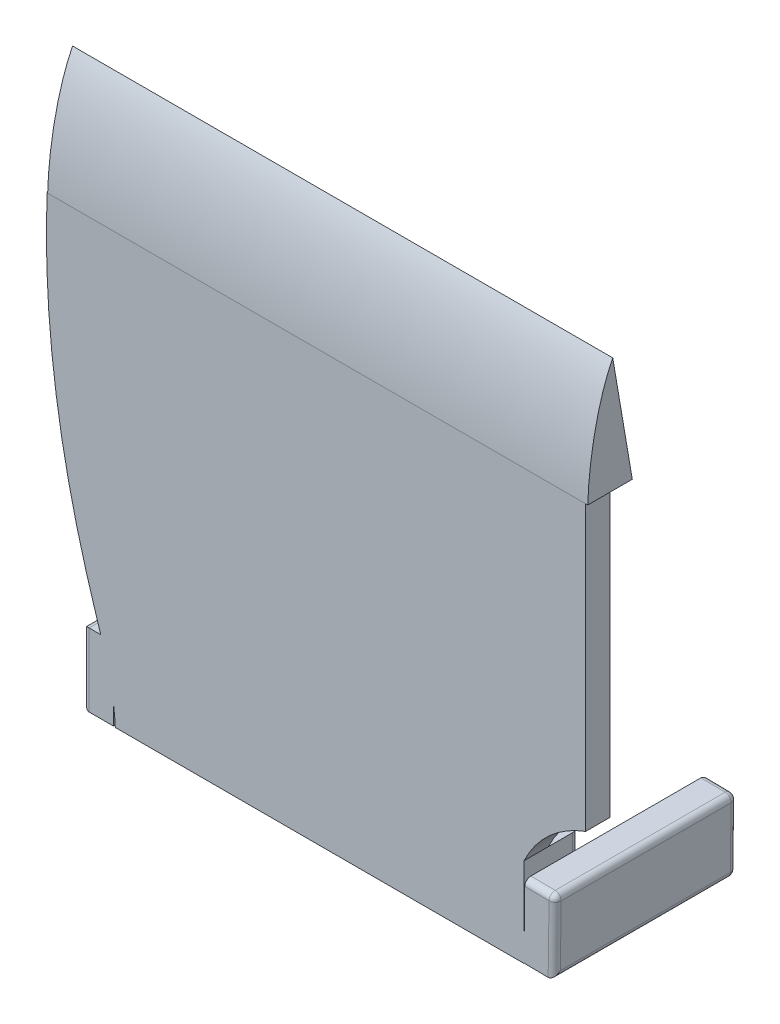
SolidWorks part; units mm, degrees
ref_plane "Front" through (0, 0, 0) normal (0, 0, 1) x (1, 0, 0)
ref_plane "Top" through (0, 0, 0) normal (0, 1, 0) x (1, 0, 0)
ref_plane "Right" through (0, 0, 0) normal (1, 0, 0) x (0, 0, -1)
sketch "Sketch1" plane through (0, 0, 0) normal (0, 0, 1) x (1, 0, 0)
  line L1 (44.1382, -8.5873) -> (44.1382, 38.1814)
  line L2 (44.1382, 38.1814) -> (-44.5905, 38.1814)
  line L3 (17.3145, -37.8937) -> (17.3145, 18.6563) construction
  line L4 (-33.6659, -37.8937) -> (-33.6659, -45.6483)
  line L8 (33.7953, -45.6483) -> (34.0118, -29.1808)
  line L9 (-33.6659, -45.6483) -> (33.7953, -45.6483)
  line L10 (34.0118, -17.8121) -> (34.0118, -29.1808)
  arc A1 (34.0118, -17.8121) -> (44.1382, -8.5873) centre (50.2048, -25.4173) cw
  spline S0 degree 3 poles (-44.5905, 38.1814) (-45.0011, 27.8073) (-43.8008, 9.7168) (-37.8707, -15.3231) (-32.3413, -29.9511) (-33.6659, -37.8937) knots 0 0 0 0 0.403328 0.698479 1 1 1 1
  dimension "D4" = 88.7287
extrude "Boss-Extrude1" add sketch "Sketch1" along normal blind 4
sketch "Sketch2" plane through (0, 0, 0) normal (1, 0, 0) x (0, 0, -1)
  line L3 (3.33, 38.1814) -> (0.1103, 57.1196)
  line L4 (0.1103, 57.1196) -> (-1.7343, 53.5468) construction
  line L5 (-1.7343, 53.5468) -> (-3.1481, 48.2225) construction
  line L6 (-4, 38.1814) -> (3.33, 38.1814)
  line L7 (-3.1481, 48.2225) -> (-3.87, 42.7778) construction
  line L8 (-3.87, 42.7778) -> (-4, 38.1814) construction
  spline S0 degree 4 poles (0.1103, 57.1196) (-1.7343, 53.5468) (-3.1481, 48.2225) (-3.87, 42.7778) (-4, 38.1814) knots 0 0 0 0 0 1 1 1 1 1
  point P2 (-1.5237, 53.8476)
  point P4 (-1.7343, 53.5468)
  point P6 (-3.1481, 48.2225)
  point P8 (-3.87, 42.7778)
  dimension "D1" = 19.21
  dimension "D4" = 7.33
extrude "Boss-Extrude2" add sketch "Sketch2" along normal mid plane 89
ref_plane "Plane1" through (0, 0, 0) normal (0, 0, -1) x (-1, 0, 0)
sketch "Sketch3" plane through (0, 0, 0) normal (0, 0, -1) x (-1, 0, 0)
  line L0 (33.6659, -45.6483) -> (-33.7953, -45.6483) construction
  line L5 (-29.0118, -17.8121) -> (-34.0118, -17.8121)
  line L6 (-29.0118, -17.8121) -> (-29.0118, -45.6483)
  line L15 (-29.0118, -45.6483) -> (-34.0118, -45.6483)
  line L17 (-34.0118, -17.8121) -> (-34.0118, -45.6483)
  line L27 (33.6659, -45.6483) -> (28.6659, -45.6483)
  line L28 (33.6659, -45.6483) -> (33.6659, -17.8121)
  line L29 (33.6659, -17.8121) -> (28.6659, -17.8121)
  line L30 (28.6659, -45.6483) -> (28.6659, -17.8121)
  dimension "D1" = 5
  dimension "D2" = 5
extrude "Boss-Extrude3" add sketch "Sketch3" along normal blind 5
ref_plane "Plane2" through (34.3896, -0.4522, 0) normal (0.9999, -0.0131, 0) x (0, 0, -1)
sketch "Sketch4" plane through (34.3896, -0.4522, 0) normal (0.9999, -0.0131, 0) x (0, 0, -1)
  line L0 (-4, -45.2) -> (-4, -28.7311) construction
  line L1 (-4, -19.9948) -> (26, -19.9948)
  line L2 (-4, -19.9948) -> (-4, -31.9948)
  line L3 (-4, -31.9948) -> (26, -31.9948)
  line L4 (26, -19.9948) -> (26, -31.9948)
  dimension "D1" = 30
  dimension "D2" = 12
extrude "Boss-Extrude4" add sketch "Sketch4" along normal blind 5
ref_plane "Plane3" through (-33.6659, 0, 0) normal (-1, 0, 0) x (0, 0, 1)
sketch "Sketch5" plane through (-33.6659, 0, 0) normal (-1, 0, 0) x (0, 0, 1)
  line L0 (4, -37.8937) -> (4, -45.6483) construction
  line L1 (-26, -20.4453) -> (4, -20.4453)
  line L2 (-26, -20.4453) -> (-26, -32.4453)
  line L3 (-26, -32.4453) -> (4, -32.4453)
  line L4 (4, -20.4453) -> (4, -32.4453)
  dimension "D1" = 12
extrude "Boss-Extrude5" add sketch "Sketch5" along normal blind 5
fillet "Fillet1" radius 1 19 edges at (34.0118, -45.6483, -2.5) (36.6265, -20.4782, 4) (38.9685, -32.51, -11) (39.0474, -26.5105, 4) (34.0118, -39.0466, -5) (36.4687, -32.4771, -26) (36.6265, -20.4782, -26) (39.1263, -20.511, -11) (39.0474, -26.5105, -26) (34.0478, -26.4448, -26) (31.5118, -45.6483, -5) (-31.1659, -45.6483, -5) (-33.6659, -20.4453, -15.5) (-38.6659, -26.4453, 4) (-38.6659, -32.4453, -11) (-33.6659, -39.0468, -5) (-38.6659, -26.4453, -26) (-33.6659, -26.4453, -26) (-38.6659, -20.4453, -11)
ref_plane "Plane4" through (34.0118, 0, 0) normal (1, 0, 0) x (0, 0, -1)
sketch "Sketch6" plane through (34.0118, 0, 0) normal (1, 0, 0) x (0, 0, -1)
  line L0 (25, -32.4969) -> (-4, -32.4969) construction
  line L1 (-7.492, -32.4969) -> (14.0862, -32.4969)
  line L2 (-7.492, -32.4969) -> (-7.492, -55.3285)
  line L3 (-7.492, -55.3285) -> (14.0862, -55.3285)
  line L4 (14.0862, -32.4969) -> (14.0862, -55.3285)
extrude "Cut-Extrude1" cut sketch "Sketch6" against normal blind 92 and the other way blind 31
